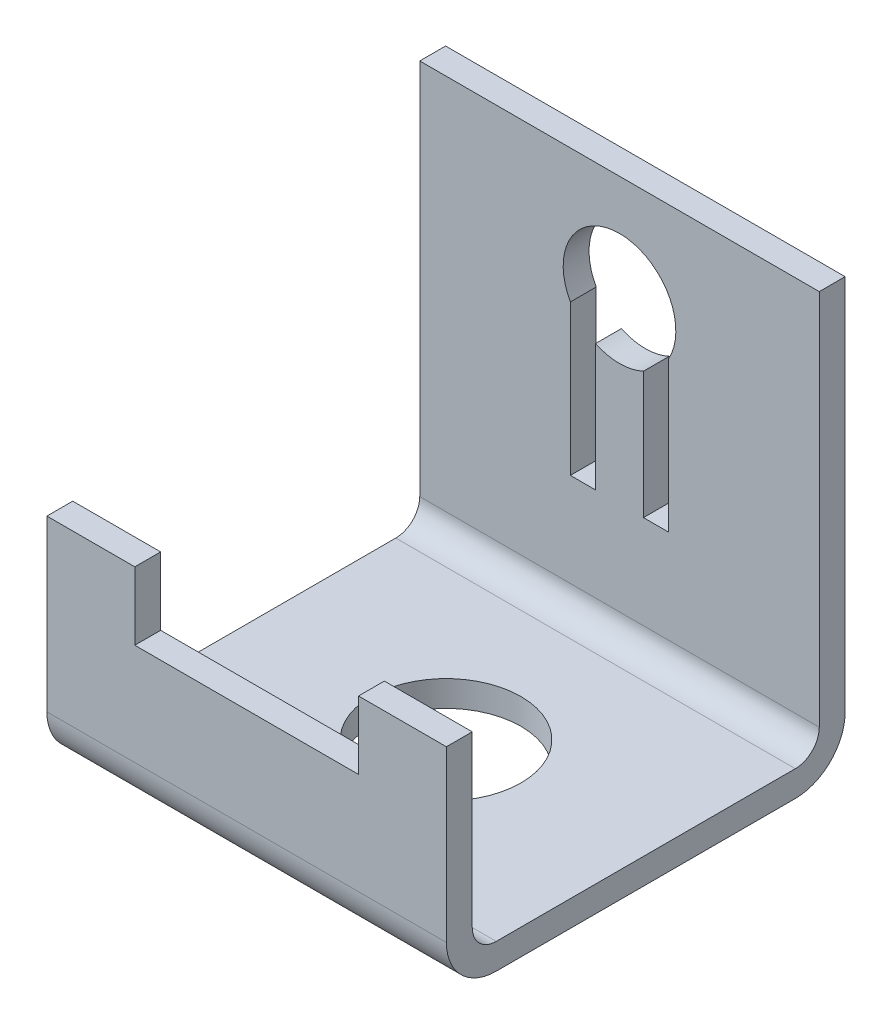
SolidWorks part; units mm, degrees
ref_plane "Front Plane" through (0, 0, 0) normal (0, 0, 1) x (1, 0, 0)
ref_plane "Top Plane" through (0, 0, 0) normal (0, 1, 0) x (1, 0, 0)
ref_plane "Right Plane" through (0, 0, 0) normal (1, 0, 0) x (0, 0, -1)
sketch "Sketch1" plane through (0, 0, 0) normal (0, 1, 0) x (1, 0, 0)
  line L1 (-12.7, 12.6746) -> (12.7, 12.6746)
  line L2 (-12.7, 12.6746) -> (-12.7, -12.6746)
  line L3 (-12.7, -12.6746) -> (12.7, -12.6746)
  line L4 (12.7, 12.6746) -> (12.7, -12.6746)
  circle A0 centre (0, 0) radius 4.7625
  dimension "D5" = 9.525
  dimension "D1" = 25.4
  dimension "D2" = 25.3492
  dimension "D3" = 12.6746
  dimension "D4" = 12.7
extrude "Boss-Extrude1" add sketch "Sketch1" along normal blind 1.6434
sketch "Sketch2" plane through (0, 1.6434, 0) normal (0, 1, 0) x (1, 0, 0)
  line L0 (-12.7, -12.6746) -> (-12.7, -11.0312)
  line L1 (-12.7, 12.6746) -> (-12.7, -12.6746) construction
  line L2 (-12.7, -11.0312) -> (12.7, -11.0312)
  line L3 (12.7, -12.6746) -> (12.7, 12.6746) construction
  line L4 (12.7, -11.0312) -> (12.7, -12.6746)
  line L5 (12.7, -12.6746) -> (-12.7, -12.6746)
  dimension "D1" = 1.6434
extrude "Boss-Extrude2" add sketch "Sketch2" along normal blind 7.9832
sketch "Sketch3" plane through (0, 9.6266, 0) normal (0, 1, 0) x (1, 0, 0)
  line L0 (-12.7, -12.6746) -> (-12.7, -11.0312)
  line L1 (-12.7, -11.0312) -> (-7.112, -11.0312)
  line L2 (12.7, -11.0312) -> (-12.7, -11.0312) construction
  line L3 (-7.112, -11.0312) -> (-7.112, -12.6746)
  line L4 (-12.7, -12.6746) -> (12.7, -12.6746) construction
  line L5 (-7.112, -12.6746) -> (-12.7, -12.6746)
  line L6 (12.7, -11.0312) -> (12.7, -12.6746)
  line L7 (12.7, -12.6746) -> (7.112, -12.6746)
  line L8 (7.112, -12.6746) -> (7.112, -11.0312)
  line L9 (7.112, -11.0312) -> (12.7, -11.0312)
  dimension "D1" = 5.588
  dimension "D2" = 5.588
  dimension "D3" = 14.224
extrude "Boss-Extrude3" add sketch "Sketch3" along normal blind 4.318
sketch "Sketch4" plane through (0, 1.6434, 0) normal (0, 1, 0) x (1, 0, 0)
  line L0 (-12.7, 12.6746) -> (12.7, 12.6746)
  line L1 (12.7, 12.6746) -> (12.7, 11.0312)
  line L2 (12.7, -11.0312) -> (12.7, 12.6746) construction
  line L3 (12.7, 11.0312) -> (-12.7, 11.0312)
  line L4 (-12.7, 12.6746) -> (-12.7, -11.0312) construction
  line L5 (-12.7, 11.0312) -> (-12.7, 12.6746)
  dimension "D1" = 1.6434
extrude "Boss-Extrude4" add sketch "Sketch4" along normal blind 25.5092
sketch "Sketch5" plane through (0, 0, -12.6746) normal (0, 0, -1) x (-1, 0, 0)
  line L0 (12.7, 27.1526) -> (12.7, 0) construction
  line L1 (-6.9864, 9.1186) -> (6.9864, 9.1186) construction
  line L2 (-12.7, 0) -> (12.7, 0) construction
  line L3 (-3.1242, 9.1186) -> (-3.1242, 18.6707)
  line L5 (-1.524, 17.1806) -> (-1.524, 9.1186)
  line L6 (-1.524, 9.1186) -> (-3.1242, 9.1186)
  line L7 (1.524, 9.1186) -> (1.524, 17.1806)
  line L9 (3.1242, 18.6707) -> (3.1242, 9.1186)
  line L10 (3.1242, 9.1186) -> (1.524, 9.1186)
  arc A0 (-1.524, 17.1806) -> (1.524, 17.1806) centre (0, 20.4216) ccw
  arc A1 (3.1242, 18.6707) -> (-3.1242, 18.6707) centre (0, 20.4216) ccw
  dimension "D2" = 7.1628
  dimension "D1" = 12.7
  dimension "D3" = 11.303
  dimension "D4" = 20.4216
  dimension "D5" = 1.6002
  dimension "D6" = 1.6002
  dimension "D7" = 6.2484
  dimension "D8" = 3.1242
extrude "Cut-Extrude1" cut sketch "Sketch5" against normal up to surface (1.6434 mm away) up to face at (0, 14.398, -11.0312)
fillet "Fillet1" radius 1.524 2 edges at (0, 1.6434, 11.0312) (0, 1.6434, -11.0312)
fillet "Fillet2" radius 3.1674 2 edges at (0, 0, -12.6746) (0, 0, 12.6746)
